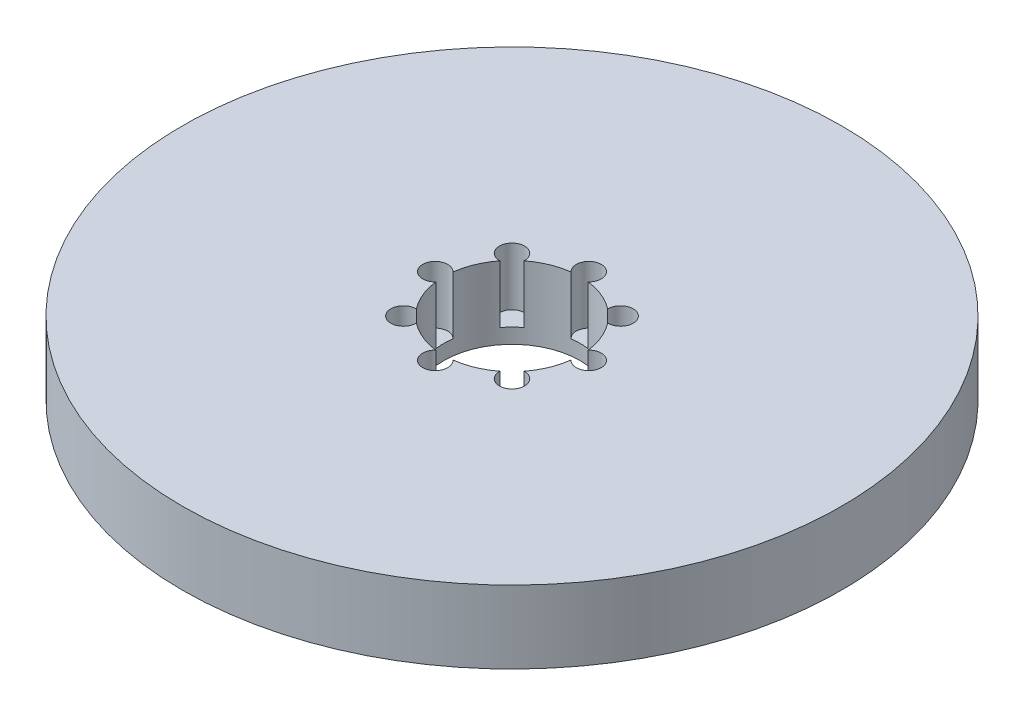
SolidWorks part; units mm, degrees
ref_plane "Front Plane" through (0, 0, 0) normal (0, 0, 1) x (1, 0, 0)
ref_plane "Top Plane" through (0, 0, 0) normal (0, 1, 0) x (1, 0, 0)
ref_plane "Right Plane" through (0, 0, 0) normal (1, 0, 0) x (0, 0, -1)
sketch "Sketch1" plane through (0, 0, 0) normal (0, 1, 0) x (1, 0, 0)
  circle A0 centre (0, 0) radius 72.5
  dimension "FLANGE_OD" = 145
extrude "Boss-Extrude1" add sketch "Sketch1" along normal blind 16
sketch "Sketch2" plane through (0, 0, 0) normal (0, 1, 0) x (1, 0, 0)
  circle A0 centre (0, 0) radius 15
  dimension "BORE_D" = 30
extrude "Cut-Extrude1" cut sketch "Sketch2" along normal through all
sketch "Sketch3" plane through (0, 16, 0) normal (0, 1, 0) x (1, 0, 0)
  circle A0 centre (0, 0) radius 16.8965 construction
  circle A1 centre (-16.8965, 0) radius 2.7657
  dimension "BOLT_D" = 5.5314
  dimension "BOLT_PCD" = 33.793
extrude "Cut-Extrude2" cut sketch "Sketch3" against normal blind 12.7117
pattern_circular "CirPattern1" count 8 over 360 about axis through (0, 0, 0) along (0, 1, 0) of "Cut-Extrude2"
